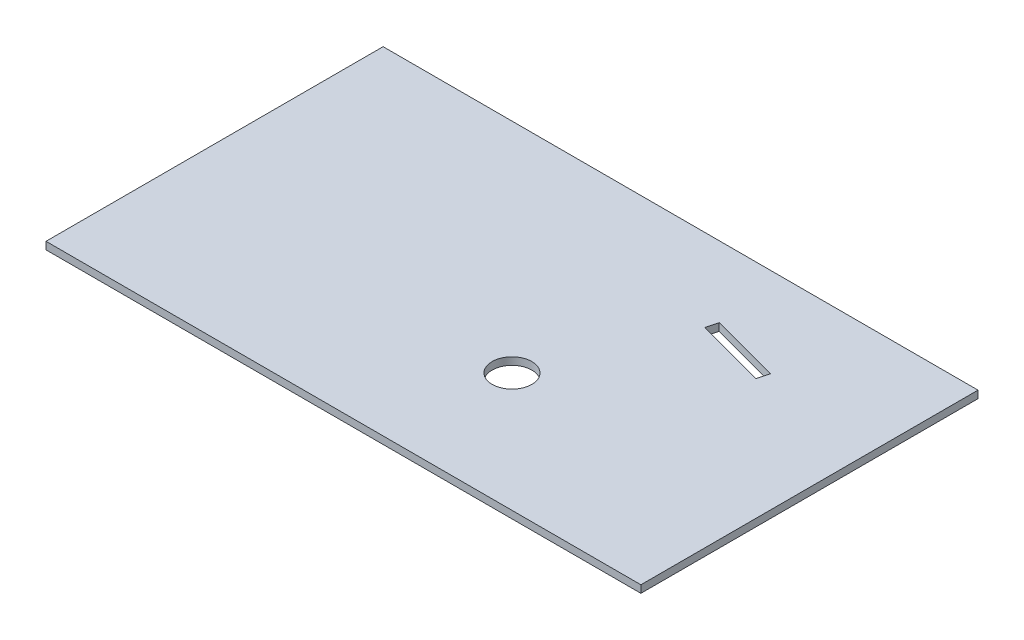
SolidWorks part; units mm, degrees
material "Particle Board"
ref_plane "Front Plane" through (0, 0, 0) normal (0, 0, 1) x (1, 0, 0)
ref_plane "Top Plane" through (0, 0, 0) normal (0, 1, 0) x (1, 0, 0)
ref_plane "Right Plane" through (0, 0, 0) normal (1, 0, 0) x (0, 0, -1)
sketch "Sketch3" plane through (0, 0, 0) normal (0, 1, 0) x (1, 0, 0)
  line L1 (0, 0) -> (-839.8654, 0) construction
  line L2 (0, 0) -> (-451.1992, 260.5) construction
  line L5 (-524, 0) -> (-525.5875, 0)
  line L6 (277.6777, 444.3772) -> (277.6777, 446.248)
  circle A0 centre (0, 0) radius 254 construction
  arc A3 (277.6777, 444.3772) -> (-524, 0) centre (0, 0) ccw
  arc A4 (277.6777, 446.248) -> (-525.5875, 0) centre (0, 0) ccw
  arc A5 (278.5189, 445.7235) -> (-525.5875, 0) centre (0, 0) ccw construction
  dimension "D1" = 524
  dimension "D2" = 1.5875
  dimension "D4" = 122
  dimension "D5" = 508
  dimension "D3" = 30
extrude "Boss-Extrude1" add sketch "Sketch3" along normal blind 50.8
sketch "Sketch4" plane through (0, 50.8, 0) normal (0, 1, 0) x (1, 0, 0)
  line L5 (-889, 558.8) -> (635, 558.8)
  line L6 (-889, 558.8) -> (-889, -304.8)
  line L7 (-889, -304.8) -> (635, -304.8)
  line L8 (635, 558.8) -> (635, -304.8)
  dimension "D1" = 304.8
  dimension "D2" = 1524
  dimension "D3" = 863.6
  dimension "D4" = 635
extrude "Boss-Extrude2" add sketch "Sketch4" along normal blind 19.05
hole_wizard "Ø20.0mm Dowel Hole1" positions "Sketch6" profile "Sketch7" hole size "Ø20.0" standard "ANSI Metric" end condition through all
sketch "Sketch6" plane through (0, 50.8, 0) normal (0, -1, 0) x (-1, 0, 0)
  point P0 (0, 0)
sketch "Sketch7" plane through (0, 50.8, 0) normal (1, 0, 0) x (0, 0, -1)
  line L0 (0, 0) -> (0, 19.05)
  line L1 (0, 19.05) -> (50.8, 19.05)
  line L2 (50.8, 19.05) -> (50.8, 0)
  line L5 (50.8, 0) -> (0, 0)
  line L11 (0, -6.35) -> (0, 107.95) construction
  dimension "Thru Hole Dia." = 101.6
  dimension "Thru Hole Depth" = 19.05
ref_plane "Plane1" through (0, 0, 298.45) normal (0, 0, 1) x (1, 0, 0)
sketch "Sketch8" plane through (0, 0, 0) normal (0, 0, 1) x (1, 0, 0)
  line L0 (-524, 50.8) -> (-524, 0) construction
  line L1 (-525.5875, 50.8) -> (-524, 50.8)
  line L2 (-525.5875, 50.8) -> (-525.5875, 0)
  line L3 (-525.5875, 0) -> (-524, 0)
  line L4 (-524, 50.8) -> (-524, 0)
  line L5 (-525.5875, 50.8) -> (-525.5875, 0) construction
  line L6 (-525.5875, 0) -> (-524, 0) construction
  line L7 (-525.5875, 50.8) -> (-524, 50.8) construction
extrude "Boss-Extrude3" add sketch "Sketch8" along normal blind 204
sketch "Sketch9" plane through (0, 50.8, 0) normal (0, -1, 0) x (-1, 0, 0)
  line L0 (-154.0683, 376.8593) -> (-332.7646, 328.9778)
  line L1 (-332.7646, 328.9778) -> (-325, 300)
  line L2 (-325, 300) -> (-146.3037, 347.8815)
  line L3 (-146.3037, 347.8815) -> (-154.0683, 376.8593)
  line L6 (0, 0) -> (-635, 0) construction
  line L7 (-635, -304.8) -> (-635, 558.8) construction
  dimension "D1" = 185
  dimension "D2" = 30
  dimension "D3" = 15
  dimension "D4" = 325
  dimension "D5" = 300
extrude "Cut-Extrude1" cut sketch "Sketch9" against normal through all
sketch "Sketch10" plane through (0, 69.85, 0) normal (0, -1, 0) x (-1, 0, 0)
  line L0 (0, 0) -> (-545.6, 0) construction
  line L1 (0, 0) -> (277.6777, 444.3772) construction
  line L2 (0, 0) -> (195.5256, 509.3615) construction
  line L3 (0, 0) -> (94.7424, 537.3111) construction
  circle A0 centre (0, 0) radius 545.6 construction
  dimension "D1" = 11
  dimension "D2" = 11
ref_axis "WHEEL CENTER" through (-965.2, 50.8, 0) along (1, 0, 0)
ref_plane "BASE CENTER" through (-127, 0, 0) normal (1, 0, 0) x (0, 0, -1)
sketch "Sketch11" plane through (0, 50.8, 0) normal (0, -1, 0) x (1, 0, 0)
  line L0 (240.5176, 138.2676) -> (268.3331, 149.5058)
  line L1 (268.3331, 149.5058) -> (296.8782, 78.8544)
  line L2 (296.8782, 78.8544) -> (269.0626, 67.6162)
  line L3 (269.0626, 67.6162) -> (240.5176, 138.2676)
  line L4 (-561.4964, -185.7671) -> (-532.9514, -256.4185)
  line L5 (-532.9514, -256.4185) -> (-505.1359, -245.1803)
  line L6 (-505.1359, -245.1803) -> (-533.6809, -174.5289)
  line L7 (-533.6809, -174.5289) -> (-561.4964, -185.7671)
  line L8 (-889, -266.954) -> (635, -266.954)
  line L9 (635, 304.8) -> (635, -558.8) construction
  line L10 (-889, -558.8) -> (-889, 304.8) construction
  line L11 (635, -558.8) -> (-889, -558.8) construction
  point P4 (-889, -368.7709)
  dimension "D1" = 30
  dimension "D2" = 30
  dimension "D3" = 291.846
